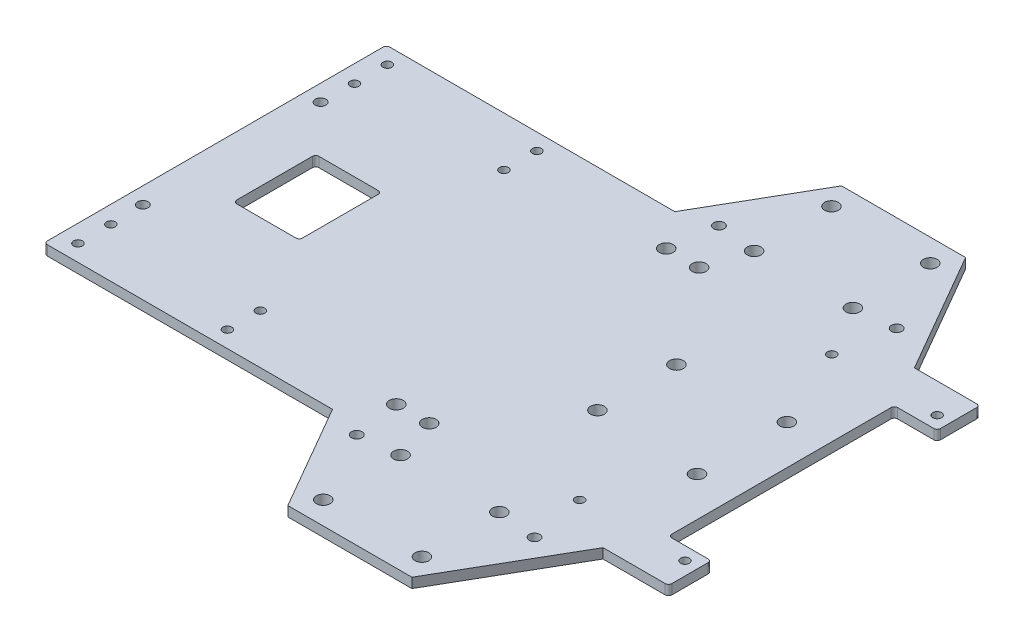
SolidWorks part; units mm, degrees
material "Acrylic (Medium-high impact)"
ref_plane "Front Plane" through (0, 0, 0) normal (0, 0, 1) x (1, 0, 0)
ref_plane "Top Plane" through (0, 0, 0) normal (0, 1, 0) x (1, 0, 0)
ref_plane "Right Plane" through (0, 0, 0) normal (1, 0, 0) x (0, 0, -1)
sketch "Sketch1" plane through (0, 0, 0) normal (0, 1, 0) x (1, 0, 0)
  line L0 (0, 52) -> (0, -52)
  line L12 (0, 52) -> (87.6171, 52)
  line L13 (87.6171, 52) -> (106.15, 84.1)
  line L14 (106.15, 84.1) -> (143.85, 84.1)
  line L15 (143.85, 84.1) -> (165.0965, 47.3)
  line L16 (165.0965, 47.3) -> (185, 47.3)
  line L17 (185, 47.3) -> (185, -47.3)
  line L18 (185, -47.3) -> (165.0965, -47.3)
  line L19 (165.0965, -47.3) -> (143.85, -84.1)
  line L20 (143.85, -84.1) -> (106.15, -84.1)
  line L21 (106.15, -84.1) -> (87.6171, -52)
  line L22 (87.6171, -52) -> (0, -52)
  line L23 (125, 84.1) -> (125, -84.1) construction
  point P12 (125, 0)
  point P15 (0, 0)
  point P23 (185, 0)
  dimension "D1" = 104
  dimension "D2" = 37.7
  dimension "D3" = 32.1
  dimension "D4" = 120
  dimension "D5" = 143.85
  dimension "D6" = 185
  dimension "D7" = 94.6
extrude "Boss-Extrude1" add sketch "Sketch1" along normal blind 3
sketch "Sketch2" plane through (0, 3, 0) normal (0, 1, 0) x (1, 0, 0)
  line L0 (87.6171, 52) -> (0, 52) construction
  line L1 (0, 52) -> (0, -52) construction
  circle A0 centre (5.3, 47) radius 1.35
  circle A1 centre (5.3, 37) radius 1.35
  circle A2 centre (50.7, 47) radius 1.35
  circle A3 centre (50.7, 37) radius 1.35
  dimension "D3" = 2.7
  dimension "D1" = 5
  dimension "D2" = 5.3
  dimension "D4" = 10
  dimension "D5" = 45.4
extrude "Motor Clevis Holes" cut sketch "Sketch2" against normal through all
mirror "Motor Clevis Holes Mirror" about plane through (0, 0, 0) normal (0, 0, 1) of "Motor Clevis Holes"
sketch "Sketch3" plane through (0, 3, 0) normal (0, 1, 0) x (1, 0, 0)
  line L0 (165.0965, -47.3) -> (185, -47.3) construction
  line L1 (185, -47.3) -> (185, 47.3) construction
  circle A0 centre (181, -38.3) radius 1.35
  circle A1 centre (149, -38.3) radius 1.35
  dimension "D1" = 2.7
  dimension "D2" = 9
  dimension "D3" = 4
  dimension "D4" = 32
extrude "Servo Clevis Holes" cut sketch "Sketch3" against normal through all
mirror "Servo Clevis Holes Mirror" about plane through (0, 0, 0) normal (0, 0, 1) of "Servo Clevis Holes"
sketch "Sketch4" plane through (0, 3, 0) normal (0, 1, 0) x (1, 0, 0)
  line L2 (0, 52) -> (0, -52) construction
  line L3 (0, -52) -> (87.6171, -52) construction
  circle A2 centre (128.1, -12) radius 2.1
  dimension "D3" = 40
  dimension "D1" = 4.2
  dimension "D2" = 128.1
extrude "Bucket Hole" cut sketch "Sketch4" against normal through all
mirror "Bucket Hole Mirror" about plane through (0, 0, 0) normal (0, 0, 1) of "Bucket Hole"
sketch "Sketch5" plane through (0, 3, 0) normal (0, 1, 0) x (1, 0, 0)
  line L0 (0, -52) -> (87.6171, -52) construction
  line L1 (0, 52) -> (0, -52) construction
  circle A0 centre (110, -53.7) radius 2.1
  circle A1 centre (110, -77.2) radius 2.1
  circle A2 centre (140, -77.2) radius 2.1
  circle A3 centre (140, -53.7) radius 2.1
  dimension "D3" = 4.2
  dimension "D1" = 1.7
  dimension "D2" = 110
  dimension "D4" = 23.5
  dimension "D5" = 30
extrude "Caster Holes" cut sketch "Sketch5" against normal through all
mirror "Caster Holes Mirror" about plane through (0, 0, 0) normal (0, 0, 1) of "Caster Holes"
sketch "Sketch6" plane through (0, 3, 0) normal (0, 1, 0) x (1, 0, 0)
  line L1 (185, -47.3) -> (185, 47.3) construction
  line L2 (165.0965, -47.3) -> (185, -47.3) construction
  line L3 (185, 34.3) -> (172, 34.3)
  line L4 (185, 34.3) -> (185, -34.3)
  line L5 (185, -34.3) -> (172, -34.3)
  line L6 (172, 34.3) -> (172, -34.3)
  point P8 (185, 0)
  point P16 (185, 0)
  dimension "D1" = 13
  dimension "D7" = 13
extrude "Front Notch" cut sketch "Sketch6" against normal through all
fillet "Fillet2" radius 1 8 edges at (185, 1.5, 47.3) (185, 1.5, 34.3) (172, 1.5, 34.3) (172, 1.5, -34.3) (185, 1.5, -34.3) (185, 1.5, -47.3) (0, 1.5, -52) (0, 1.5, 52)
sketch "Sketch9" plane through (0, 3, 0) normal (0, 1, 0) x (1, 0, 0)
  line L0 (0, 51) -> (0, -51) construction
  line L1 (106, -41) -> (106, 41) construction
  circle A0 centre (106, 41) radius 2.1
  circle A1 centre (96, 41) radius 2.1
  circle A2 centre (106, -41) radius 2.1
  circle A3 centre (96, -41) radius 2.1
  point P6 (106, 0)
  dimension "D3" = 4.2
  dimension "D4" = 10
  dimension "D1" = 106
  dimension "D2" = 82
extrude "Color Sensor Bracket Holes" cut sketch "Sketch9" against normal through all
sketch "Sketch10" plane through (0, 3, 0) normal (0, 1, 0) x (1, 0, 0)
  line L1 (18, -12.5) -> (38, -12.5)
  line L2 (18, -12.5) -> (18, 12.5)
  line L3 (18, 12.5) -> (38, 12.5)
  line L4 (38, -12.5) -> (38, 12.5)
  line L5 (18, -12.5) -> (38, 12.5) construction
  line L6 (18, 12.5) -> (38, -12.5) construction
  point P0 (28, 0)
  point P3 (28, 0)
  dimension "D1" = 28
  dimension "D2" = 20
  dimension "D3" = 25
extrude "Motor Routing Pocket" cut sketch "Sketch10" against normal through all
fillet "Fillet3" radius 1 4 edges at (18, 1.5, 12.5) (38, 1.5, 12.5) (38, 1.5, -12.5) (18, 1.5, -12.5)
sketch "Sketch11" plane through (0, 3, 0) normal (0, 1, 0) x (1, 0, 0)
  line L0 (0, 51) -> (0, -51) construction
  circle A0 centre (5, 27) radius 1.6
  circle A1 centre (5, -27) radius 1.6
  circle A2 centre (98, -55) radius 1.6
  circle A3 centre (98, 55) radius 1.6
  circle A4 centre (152, -55) radius 1.6
  circle A5 centre (152, 55) radius 1.6
  point P13 (0, 0)
  dimension "D1" = 3.2
  dimension "D2" = 5
  dimension "D3" = 27
  dimension "D4" = 27
  dimension "D5" = 98
  dimension "D6" = 55
  dimension "D7" = 55
  dimension "D8" = 54
extrude "Plate Standoff Holes" cut sketch "Sketch11" against normal through all
sketch "Sketch12" plane through (0, 3, 0) normal (0, 1, 0) x (1, 0, 0)
  line L0 (160, 13.65) -> (160, -13.65) construction
  line L2 (172, 33.3) -> (172, -33.3) construction
  circle A0 centre (160, 13.65) radius 2.1
  circle A1 centre (160, -13.65) radius 2.1
  point P4 (160, 0)
  point P5 (166.3215, 16.65)
  dimension "D1" = 4.2
  dimension "D2" = 27.3
  dimension "D3" = 12
extrude "Ultrasonic Sensor Mount Holes" cut sketch "Sketch12" against normal through all
equation "\"D7@Sketch11\"=\"D6@Sketch11\""
equation "\"D4@Sketch11\"=\"D3@Sketch11\""
